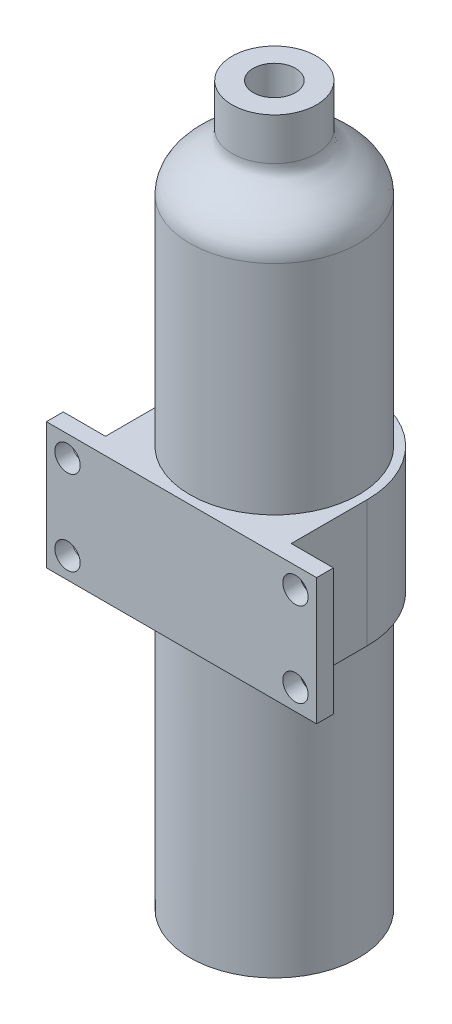
SolidWorks part; units mm, degrees
ref_plane "Alzado" through (0, 0, 0) normal (0, 0, 1) x (1, 0, 0)
ref_plane "Planta" through (0, 0, 0) normal (0, 1, 0) x (1, 0, 0)
ref_plane "Vista lateral" through (0, 0, 0) normal (1, 0, 0) x (0, 0, -1)
sketch "Croquis3" plane through (0, 0, 0) normal (0, 0, 1) x (1, 0, 0)
  line L0 (0, 0) -> (0, 80) construction
  line L1 (0, 80) -> (5, 80) construction
  line L3 (10, 73.2783) -> (10, 0)
  line L4 (10, 0) -> (0, 0)
  line L5 (0, 0) -> (0, 80)
  line L6 (0, 80) -> (5, 80)
  line L7 (10, 42.3793) -> (10, 44.6739) construction
  line L8 (5, 78.1941) -> (5, 79.7862) construction
  spline S0 degree 3 poles (5, 80) (5, 79.0049) (5.6792, 78.3381) (8.8641, 76.2963) (10, 74.7125) (10, 73.2783) knots 0 0 0 0 0.19722 0.426407 1 1 1 1
  dimension "D1" = 80
  dimension "D2" = 10
  dimension "D3" = 5
  dimension "D4" = 3.7257
  dimension "D5" = 5.0661
  dimension "D6" = 1.6555
  dimension "D7" = 2.3486
  dimension "D8" = 1.8779
revolve "Revolución2" add sketch "Croquis3" angle 360 about L5
sketch "Croquis4" plane through (0, 80, 0) normal (0, 1, 0) x (1, 0, 0)
  circle A0 centre (0, 0) radius 5
  dimension "D1" = 10
extrude "Saliente-Extruir1" add sketch "Croquis4" along normal blind 5
sketch "Croquis5" plane through (0, 85, 0) normal (0, 1, 0) x (1, 0, 0)
  circle A0 centre (0, 0) radius 2.5
  dimension "D1" = 5
extrude "Cortar-Extruir1" cut sketch "Croquis5" against normal blind 10
shell "Vaciado2" thickness 2 removed face at (0, 75, 2.5)
ref_plane "Plano1" through (0, 40, 0) normal (0, 1, 0) x (1, 0, 0)
sketch "Croquis6" plane through (0, 40, 0) normal (0, 1, 0) x (1, 0, 0)
  line L0 (-11, 0) -> (-11, -9)
  line L1 (-11, -9) -> (-16, -9)
  line L2 (-16, -9) -> (-16, -11)
  line L3 (-16, -11) -> (16, -11)
  line L4 (16, -11) -> (16, -9)
  line L5 (16, -9) -> (11, -9)
  line L6 (11, -9) -> (11, 0)
  circle A0 centre (0, 0) radius 9
  arc A1 (11, 0) -> (-11, 0) centre (0, 0) ccw
  dimension "D1" = 18
  dimension "D2" = 22
  dimension "D3" = 2
  dimension "D4" = 5
extrude "Saliente-Extruir2" add sketch "Croquis6" along normal mid plane 15
sketch "Croquis7" plane through (0, 0, 9) normal (0, 0, -1) x (-1, 0, 0)
  line L0 (16, 40) -> (-16, 40) construction
  line L1 (16, 47.5) -> (16, 32.5) construction
  line L2 (-16, 47.5) -> (-16, 32.5) construction
  line L3 (-13.5, 35) -> (-13.5, 45) construction
  line L4 (13.5, 35) -> (13.5, 45) construction
  circle A0 centre (-13.5, 45) radius 1.5
  circle A1 centre (-13.5, 35) radius 1.5
  circle A2 centre (13.5, 35) radius 1.5
  circle A3 centre (13.5, 45) radius 1.5
  point P9 (-13.5, 40)
  point P12 (13.5, 40)
  dimension "D4" = 3
  dimension "D1" = 10
  dimension "D2" = 2.5
  dimension "D3" = 2.5
extrude "Cortar-Extruir2" cut sketch "Croquis7" against normal through all
